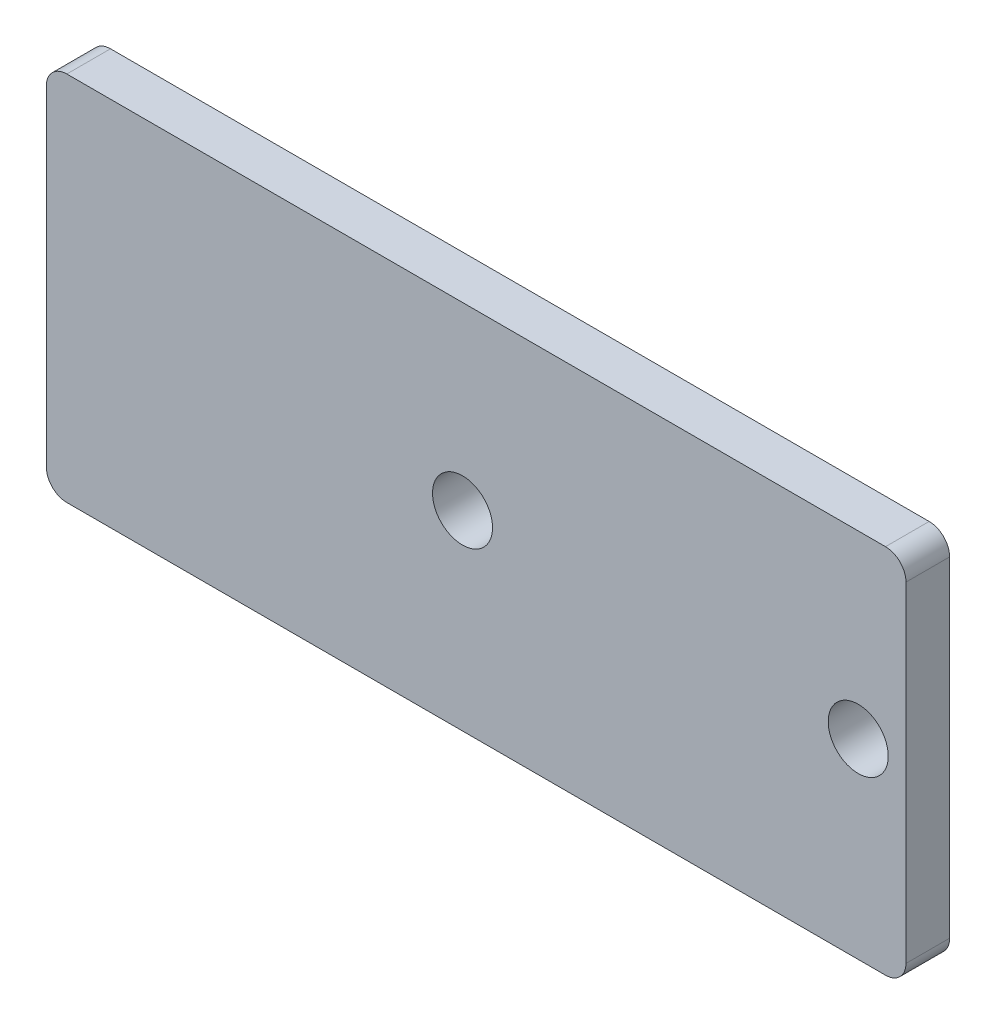
SolidWorks part; units mm, degrees
material "FR4_stuffedProtoboard"
ref_plane "Front Plane" through (0, 0, 0) normal (0, 0, 1) x (1, 0, 0)
ref_plane "Top Plane" through (0, 0, 0) normal (0, 1, 0) x (1, 0, 0)
ref_plane "Right Plane" through (0, 0, 0) normal (1, 0, 0) x (0, 0, -1)
sketch "Model" plane through (0, 0, 0) normal (0, 0, 1) x (1, 0, 0)
  line L0 (-15, -6.8) -> (15, -6.8)
  line L1 (15.75, -6.05) -> (15.75, 6.05)
  line L2 (-15, 6.8) -> (15, 6.8)
  line L3 (-15.75, 6.05) -> (-15.75, -6.05)
  arc A0 (-15, 6.8) -> (-15.75, 6.05) centre (-15, 6.05) ccw
  arc A1 (15, 6.8) -> (15.75, 6.05) centre (15, 6.05) cw
  arc A2 (15, -6.8) -> (15.75, -6.05) centre (15, -6.05) ccw
  arc A3 (-15, -6.8) -> (-15.75, -6.05) centre (-15, -6.05) cw
  circle A4 centre (-0.5, 0.2) radius 1.1
  circle A5 centre (14, 0.2) radius 1.1
  point P2 (0, -6.8)
  point P7 (-15.75, 6.8)
  point P17 (15.75, -6.8)
  point P20 (-15.75, -6.8)
  point P24 (15.75, 0)
  dimension "D3" = 7
  dimension "D7" = 31.5
  dimension "D8" = 2.2
  dimension "D9" = 2.2
  dimension "D1" = 0.75
  dimension "D2" = 13.6
  dimension "D5" = 14.5
  dimension "D6" = 1.75
extrude "Boss-Extrude1" add sketch "Model" along normal mid plane 1.6
sketch "Sketch1" plane through (0, 0, 0.8) normal (0, 0, 1) x (1, 0, 0)
  line L1 (-13.75, 5.2) -> (-3.75, 5.2)
  line L2 (-13.75, 5.2) -> (-13.75, -4.8)
  line L3 (-13.75, -4.8) -> (-3.75, -4.8)
  line L4 (-3.75, 5.2) -> (-3.75, -4.8)
  line L5 (-15.75, 6.05) -> (-15.75, -6.05) construction
  line L7 (-15, -6.8) -> (15, -6.8) construction
  dimension "D1" = 2
  dimension "D2" = 2
  dimension "D3" = 10
  dimension "D4" = 10
